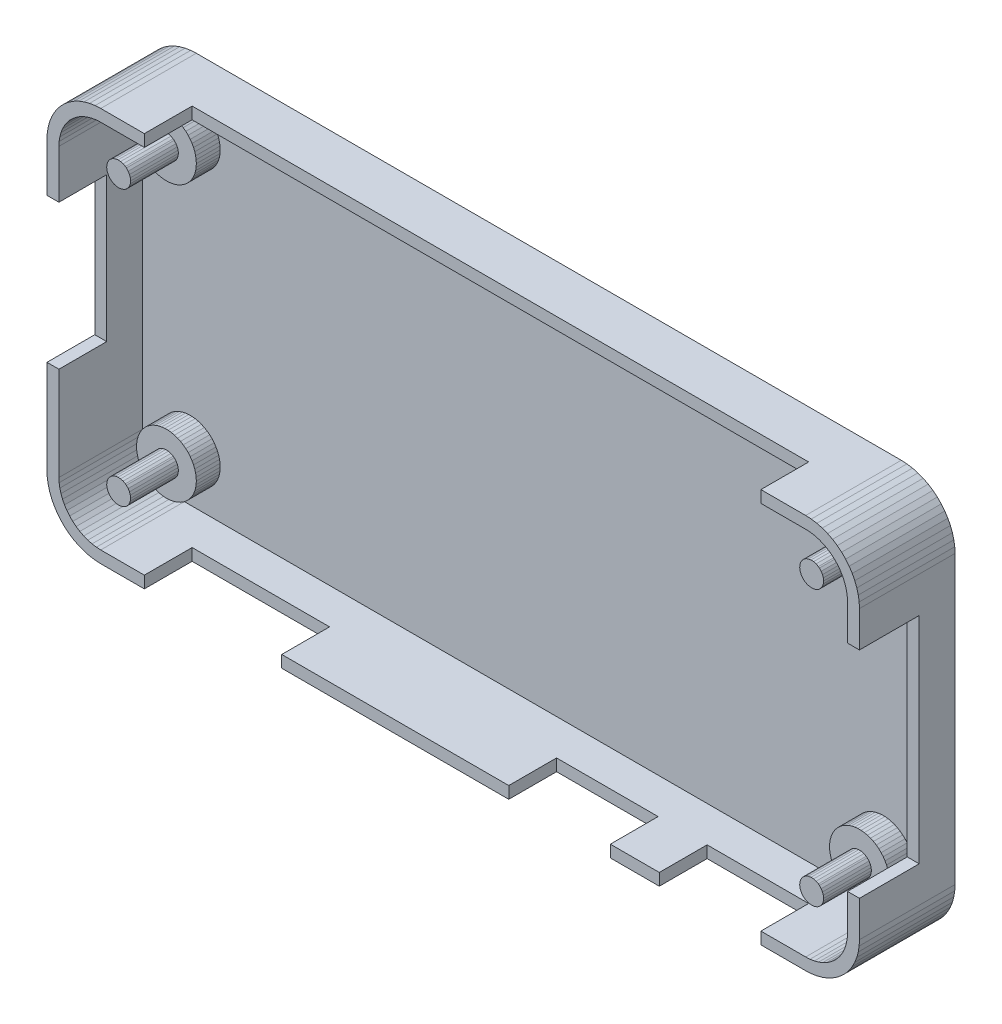
SolidWorks part; units mm, degrees
ref_plane "Front Plane" through (0, 0, 0) normal (0, 0, 1) x (1, 0, 0)
ref_plane "Top Plane" through (0, 0, 0) normal (0, 1, 0) x (1, 0, 0)
ref_plane "Right Plane" through (0, 0, 0) normal (1, 0, 0) x (0, 0, -1)
ref_plane "Plane1" through (0, 0, 0) normal (0, 0, -1) x (-1, 0, 0)
sketch "Sketch1" plane through (0, 0, 0) normal (0, 0, -1) x (-1, 0, 0)
  line L0 (29.5, 16.5) -> (-29.5, 16.5)
  line L1 (-29.5, 16.5) -> (-29.9704, 16.4753)
  line L2 (-29.9704, 16.4753) -> (-30.4356, 16.4017)
  line L3 (-30.4356, 16.4017) -> (-30.8906, 16.2798)
  line L4 (-30.8906, 16.2798) -> (-31.3303, 16.111)
  line L5 (-31.3303, 16.111) -> (-31.75, 15.8971)
  line L6 (-31.75, 15.8971) -> (-32.145, 15.6406)
  line L7 (-32.145, 15.6406) -> (-32.5111, 15.3442)
  line L8 (-32.5111, 15.3442) -> (-32.8442, 15.0111)
  line L9 (-32.8442, 15.0111) -> (-33.1406, 14.645)
  line L10 (-33.1406, 14.645) -> (-33.3971, 14.25)
  line L11 (-33.3971, 14.25) -> (-33.611, 13.8303)
  line L12 (-33.611, 13.8303) -> (-33.7798, 13.3906)
  line L13 (-33.7798, 13.3906) -> (-33.9017, 12.9356)
  line L14 (-33.9017, 12.9356) -> (-33.9753, 12.4704)
  line L15 (-33.9753, 12.4704) -> (-34, 12)
  line L16 (-34, 12) -> (-34, -12)
  line L17 (-34, -12) -> (-33.9753, -12.4704)
  line L18 (-33.9753, -12.4704) -> (-33.9017, -12.9356)
  line L19 (-33.9017, -12.9356) -> (-33.7798, -13.3906)
  line L20 (-33.7798, -13.3906) -> (-33.611, -13.8303)
  line L21 (-33.611, -13.8303) -> (-33.3971, -14.25)
  line L22 (-33.3971, -14.25) -> (-33.1406, -14.645)
  line L23 (-33.1406, -14.645) -> (-32.8442, -15.0111)
  line L24 (-32.8442, -15.0111) -> (-32.5111, -15.3442)
  line L25 (-32.5111, -15.3442) -> (-32.145, -15.6406)
  line L26 (-32.145, -15.6406) -> (-31.75, -15.8971)
  line L27 (-31.75, -15.8971) -> (-31.3303, -16.111)
  line L28 (-31.3303, -16.111) -> (-30.8906, -16.2798)
  line L29 (-30.8906, -16.2798) -> (-30.4356, -16.4017)
  line L30 (-30.4356, -16.4017) -> (-29.9704, -16.4753)
  line L31 (-29.9704, -16.4753) -> (-29.5, -16.5)
  line L32 (-29.5, -16.5) -> (29.5, -16.5)
  line L33 (29.5, -16.5) -> (29.9704, -16.4753)
  line L34 (29.9704, -16.4753) -> (30.4356, -16.4017)
  line L35 (30.4356, -16.4017) -> (30.8906, -16.2798)
  line L36 (30.8906, -16.2798) -> (31.3303, -16.111)
  line L37 (31.3303, -16.111) -> (31.75, -15.8971)
  line L38 (31.75, -15.8971) -> (32.145, -15.6406)
  line L39 (32.145, -15.6406) -> (32.5111, -15.3442)
  line L40 (32.5111, -15.3442) -> (32.8442, -15.0111)
  line L41 (32.8442, -15.0111) -> (33.1406, -14.645)
  line L42 (33.1406, -14.645) -> (33.3971, -14.25)
  line L43 (33.3971, -14.25) -> (33.611, -13.8303)
  line L44 (33.611, -13.8303) -> (33.7798, -13.3906)
  line L45 (33.7798, -13.3906) -> (33.9017, -12.9356)
  line L46 (33.9017, -12.9356) -> (33.9753, -12.4704)
  line L47 (33.9753, -12.4704) -> (34, -12)
  line L48 (34, -12) -> (34, 12)
  line L49 (34, 12) -> (33.9753, 12.4704)
  line L50 (33.9753, 12.4704) -> (33.9017, 12.9356)
  line L51 (33.9017, 12.9356) -> (33.7798, 13.3906)
  line L52 (33.7798, 13.3906) -> (33.611, 13.8303)
  line L53 (33.611, 13.8303) -> (33.3971, 14.25)
  line L54 (33.3971, 14.25) -> (33.1406, 14.645)
  line L55 (33.1406, 14.645) -> (32.8442, 15.0111)
  line L56 (32.8442, 15.0111) -> (32.5111, 15.3442)
  line L57 (32.5111, 15.3442) -> (32.145, 15.6406)
  line L58 (32.145, 15.6406) -> (31.75, 15.8971)
  line L59 (31.75, 15.8971) -> (31.3303, 16.111)
  line L60 (31.3303, 16.111) -> (30.8906, 16.2798)
  line L61 (30.8906, 16.2798) -> (30.4356, 16.4017)
  line L62 (30.4356, 16.4017) -> (29.9704, 16.4753)
  line L63 (29.9704, 16.4753) -> (29.5, 16.5)
extrude "Boss-Extrude1" add sketch "Sketch1" against normal blind 8
sketch "Sketch2" plane through (0, 0, 8) normal (0, 0, 1) x (1, 0, 0)
  line L0 (-30.5816, -15.3287) -> (-30.2277, -15.4235)
  line L1 (-30.2277, -15.4235) -> (-29.8658, -15.4808)
  line L2 (-29.8658, -15.4808) -> (-29.5, -15.5)
  line L3 (-29.5, -15.5) -> (29.5, -15.5)
  line L4 (29.5, -15.5) -> (29.8658, -15.4808)
  line L5 (29.8658, -15.4808) -> (30.2277, -15.4235)
  line L6 (30.2277, -15.4235) -> (30.5816, -15.3287)
  line L7 (30.5816, -15.3287) -> (30.9236, -15.1974)
  line L8 (30.9236, -15.1974) -> (31.25, -15.0311)
  line L9 (31.25, -15.0311) -> (31.5572, -14.8316)
  line L10 (31.5572, -14.8316) -> (31.842, -14.601)
  line L11 (31.842, -14.601) -> (32.101, -14.342)
  line L12 (32.101, -14.342) -> (32.3316, -14.0572)
  line L13 (32.3316, -14.0572) -> (32.5311, -13.75)
  line L14 (32.5311, -13.75) -> (32.6974, -13.4236)
  line L15 (32.6974, -13.4236) -> (32.8287, -13.0816)
  line L16 (32.8287, -13.0816) -> (32.9235, -12.7277)
  line L17 (32.9235, -12.7277) -> (32.9808, -12.3658)
  line L18 (32.9808, -12.3658) -> (33, -12)
  line L19 (33, -12) -> (33, 12)
  line L20 (33, 12) -> (32.9808, 12.3658)
  line L21 (32.9808, 12.3658) -> (32.9235, 12.7277)
  line L22 (32.9235, 12.7277) -> (32.8287, 13.0816)
  line L23 (32.8287, 13.0816) -> (32.6974, 13.4236)
  line L24 (32.6974, 13.4236) -> (32.5311, 13.75)
  line L25 (32.5311, 13.75) -> (32.3316, 14.0572)
  line L26 (32.3316, 14.0572) -> (32.101, 14.342)
  line L27 (32.101, 14.342) -> (31.842, 14.601)
  line L28 (31.842, 14.601) -> (31.5572, 14.8316)
  line L29 (31.5572, 14.8316) -> (31.25, 15.0311)
  line L30 (31.25, 15.0311) -> (30.9236, 15.1974)
  line L31 (30.9236, 15.1974) -> (30.5816, 15.3287)
  line L32 (30.5816, 15.3287) -> (30.2277, 15.4235)
  line L33 (30.2277, 15.4235) -> (29.8658, 15.4808)
  line L34 (29.8658, 15.4808) -> (29.5, 15.5)
  line L35 (29.5, 15.5) -> (-29.5, 15.5)
  line L36 (-29.5, 15.5) -> (-29.8658, 15.4808)
  line L37 (-29.8658, 15.4808) -> (-30.2277, 15.4235)
  line L38 (-30.2277, 15.4235) -> (-30.5816, 15.3287)
  line L39 (-30.5816, 15.3287) -> (-30.9236, 15.1974)
  line L40 (-30.9236, 15.1974) -> (-31.25, 15.0311)
  line L41 (-31.25, 15.0311) -> (-31.5572, 14.8316)
  line L42 (-31.5572, 14.8316) -> (-31.842, 14.601)
  line L43 (-31.842, 14.601) -> (-32.101, 14.342)
  line L44 (-32.101, 14.342) -> (-32.3316, 14.0572)
  line L45 (-32.3316, 14.0572) -> (-32.5311, 13.75)
  line L46 (-32.5311, 13.75) -> (-32.6974, 13.4236)
  line L47 (-32.6974, 13.4236) -> (-32.8287, 13.0816)
  line L48 (-32.8287, 13.0816) -> (-32.9235, 12.7277)
  line L49 (-32.9235, 12.7277) -> (-32.9808, 12.3658)
  line L50 (-32.9808, 12.3658) -> (-33, 12)
  line L51 (-33, 12) -> (-33, -12)
  line L52 (-33, -12) -> (-32.9808, -12.3658)
  line L53 (-32.9808, -12.3658) -> (-32.9235, -12.7277)
  line L54 (-32.9235, -12.7277) -> (-32.8287, -13.0816)
  line L55 (-32.8287, -13.0816) -> (-32.6974, -13.4236)
  line L56 (-32.6974, -13.4236) -> (-32.5311, -13.75)
  line L57 (-32.5311, -13.75) -> (-32.3316, -14.0572)
  line L58 (-32.3316, -14.0572) -> (-32.101, -14.342)
  line L59 (-32.101, -14.342) -> (-31.842, -14.601)
  line L60 (-31.842, -14.601) -> (-31.5572, -14.8316)
  line L61 (-31.5572, -14.8316) -> (-31.25, -15.0311)
  line L62 (-31.25, -15.0311) -> (-30.9236, -15.1974)
  line L63 (-30.9236, -15.1974) -> (-30.5816, -15.3287)
extrude "Cut-Extrude1" cut sketch "Sketch2" against normal blind 7
sketch "Sketch3" plane through (0, -16.5, 0) normal (0, -1, 0) x (1, 0, 0)
  line L0 (-14.35, 8) -> (-25.85, 8)
  line L1 (-25.85, 8) -> (-25.85, 4)
  line L2 (-25.85, 4) -> (-14.35, 4)
  line L3 (-14.35, 4) -> (-14.35, 8)
extrude "Cut-Extrude2" cut sketch "Sketch3" against normal up to next
sketch "Sketch4" plane through (0, -16.5, 0) normal (0, -1, 0) x (1, 0, 0)
  line L0 (13.15, 8) -> (4.65, 8)
  line L1 (4.65, 8) -> (4.65, 4)
  line L2 (4.65, 4) -> (13.15, 4)
  line L3 (13.15, 4) -> (13.15, 8)
extrude "Cut-Extrude3" cut sketch "Sketch4" against normal up to next
sketch "Sketch5" plane through (0, -16.5, 0) normal (0, -1, 0) x (1, 0, 0)
  line L0 (25.75, 8) -> (17.25, 8)
  line L1 (17.25, 8) -> (17.25, 4)
  line L2 (17.25, 4) -> (25.75, 4)
  line L3 (25.75, 4) -> (25.75, 8)
extrude "Cut-Extrude4" cut sketch "Sketch5" against normal up to next
sketch "Sketch6" plane through (-34, 0, 0) normal (-1, 0, 0) x (0, 0, 1)
  line L0 (8, -4.15) -> (8, 7.95)
  line L1 (8, 7.95) -> (4, 7.95)
  line L2 (4, 7.95) -> (4, -4.15)
  line L3 (4, -4.15) -> (8, -4.15)
extrude "Cut-Extrude5" cut sketch "Sketch6" against normal up to next
sketch "Sketch7" plane through (34, 0, 0) normal (1, 0, 0) x (0, 0, -1)
  line L0 (-8, 9) -> (-8, -9)
  line L1 (-8, -9) -> (-3, -9)
  line L2 (-3, -9) -> (-3, 9)
  line L3 (-3, 9) -> (-8, 9)
extrude "Cut-Extrude6" cut sketch "Sketch7" against normal up to next
sketch "Sketch8" plane through (0, 0, 1) normal (0, 0, 1) x (1, 0, 0)
  line L0 (-29.4045, -9.0329) -> (-29.1353, -9.0037)
  line L1 (-29.1353, -9.0037) -> (-28.8647, -9.0037)
  line L2 (-28.8647, -9.0037) -> (-28.5955, -9.0329)
  line L3 (-28.5955, -9.0329) -> (-28.3312, -9.0911)
  line L4 (-28.3312, -9.0911) -> (-28.0747, -9.1776)
  line L5 (-28.0747, -9.1776) -> (-27.829, -9.2912)
  line L6 (-27.829, -9.2912) -> (-27.597, -9.4308)
  line L7 (-27.597, -9.4308) -> (-27.3815, -9.5946)
  line L8 (-27.3815, -9.5946) -> (-27.185, -9.7808)
  line L9 (-27.185, -9.7808) -> (-27.0098, -9.9871)
  line L10 (-27.0098, -9.9871) -> (-26.8579, -10.2111)
  line L11 (-26.8579, -10.2111) -> (-26.7311, -10.4503)
  line L12 (-26.7311, -10.4503) -> (-26.6309, -10.7017)
  line L13 (-26.6309, -10.7017) -> (-26.5584, -10.9626)
  line L14 (-26.5584, -10.9626) -> (-26.5147, -11.2297)
  line L15 (-26.5147, -11.2297) -> (-26.5, -11.5)
  line L16 (-26.5, -11.5) -> (-26.5147, -11.7703)
  line L17 (-26.5147, -11.7703) -> (-26.5584, -12.0374)
  line L18 (-26.5584, -12.0374) -> (-26.6309, -12.2983)
  line L19 (-26.6309, -12.2983) -> (-26.7311, -12.5497)
  line L20 (-26.7311, -12.5497) -> (-26.8579, -12.7889)
  line L21 (-26.8579, -12.7889) -> (-27.0098, -13.0129)
  line L22 (-27.0098, -13.0129) -> (-27.185, -13.2192)
  line L23 (-27.185, -13.2192) -> (-27.3815, -13.4054)
  line L24 (-27.3815, -13.4054) -> (-27.597, -13.5692)
  line L25 (-27.597, -13.5692) -> (-27.829, -13.7088)
  line L26 (-27.829, -13.7088) -> (-28.0747, -13.8224)
  line L27 (-28.0747, -13.8224) -> (-28.3312, -13.9089)
  line L28 (-28.3312, -13.9089) -> (-28.5955, -13.9671)
  line L29 (-28.5955, -13.9671) -> (-28.8647, -13.9963)
  line L30 (-28.8647, -13.9963) -> (-29.1353, -13.9963)
  line L31 (-29.1353, -13.9963) -> (-29.4045, -13.9671)
  line L32 (-29.4045, -13.9671) -> (-29.6688, -13.9089)
  line L33 (-29.6688, -13.9089) -> (-29.9253, -13.8224)
  line L34 (-29.9253, -13.8224) -> (-30.171, -13.7088)
  line L35 (-30.171, -13.7088) -> (-30.403, -13.5692)
  line L36 (-30.403, -13.5692) -> (-30.6185, -13.4054)
  line L37 (-30.6185, -13.4054) -> (-30.815, -13.2192)
  line L38 (-30.815, -13.2192) -> (-30.9902, -13.0129)
  line L39 (-30.9902, -13.0129) -> (-31.1421, -12.7889)
  line L40 (-31.1421, -12.7889) -> (-31.2689, -12.5497)
  line L41 (-31.2689, -12.5497) -> (-31.3691, -12.2983)
  line L42 (-31.3691, -12.2983) -> (-31.4416, -12.0374)
  line L43 (-31.4416, -12.0374) -> (-31.4853, -11.7703)
  line L44 (-31.4853, -11.7703) -> (-31.5, -11.5)
  line L45 (-31.5, -11.5) -> (-31.4853, -11.2297)
  line L46 (-31.4853, -11.2297) -> (-31.4416, -10.9626)
  line L47 (-31.4416, -10.9626) -> (-31.3691, -10.7017)
  line L48 (-31.3691, -10.7017) -> (-31.2689, -10.4503)
  line L49 (-31.2689, -10.4503) -> (-31.1421, -10.2111)
  line L50 (-31.1421, -10.2111) -> (-30.9902, -9.9871)
  line L51 (-30.9902, -9.9871) -> (-30.815, -9.7808)
  line L52 (-30.815, -9.7808) -> (-30.6185, -9.5946)
  line L53 (-30.6185, -9.5946) -> (-30.403, -9.4308)
  line L54 (-30.403, -9.4308) -> (-30.171, -9.2912)
  line L55 (-30.171, -9.2912) -> (-29.9253, -9.1776)
  line L56 (-29.9253, -9.1776) -> (-29.6688, -9.0911)
  line L57 (-29.6688, -9.0911) -> (-29.4045, -9.0329)
extrude "Boss-Extrude2" add sketch "Sketch8" along normal blind 2
sketch "Sketch9" plane through (0, 0, 3) normal (0, 0, 1) x (1, 0, 0)
  line L0 (-29.9076, -11.0801) -> (-29.7961, -10.8948)
  line L1 (-29.7961, -10.8948) -> (-29.6474, -10.7378)
  line L2 (-29.6474, -10.7378) -> (-29.4684, -10.6165)
  line L3 (-29.4684, -10.6165) -> (-29.2675, -10.5364)
  line L4 (-29.2675, -10.5364) -> (-29.0541, -10.5015)
  line L5 (-29.0541, -10.5015) -> (-28.8382, -10.5132)
  line L6 (-28.8382, -10.5132) -> (-28.6299, -10.571)
  line L7 (-28.6299, -10.571) -> (-28.3903, -10.698)
  line L8 (-28.3903, -10.698) -> (-28.2039, -10.8948)
  line L9 (-28.2039, -10.8948) -> (-28.0924, -11.0801)
  line L10 (-28.0924, -11.0801) -> (-28.0234, -11.285)
  line L11 (-28.0234, -11.285) -> (-28, -11.5)
  line L12 (-28, -11.5) -> (-28.0234, -11.715)
  line L13 (-28.0234, -11.715) -> (-28.0924, -11.9199)
  line L14 (-28.0924, -11.9199) -> (-28.2039, -12.1052)
  line L15 (-28.2039, -12.1052) -> (-28.3526, -12.2622)
  line L16 (-28.3526, -12.2622) -> (-28.4388, -12.3277)
  line L17 (-28.4388, -12.3277) -> (-28.5316, -12.3835)
  line L18 (-28.5316, -12.3835) -> (-28.7325, -12.4635)
  line L19 (-28.7325, -12.4635) -> (-28.9459, -12.4985)
  line L20 (-28.9459, -12.4985) -> (-29.1618, -12.4868)
  line L21 (-29.1618, -12.4868) -> (-29.3701, -12.429)
  line L22 (-29.3701, -12.429) -> (-29.5612, -12.3277)
  line L23 (-29.5612, -12.3277) -> (-29.726, -12.1877)
  line L24 (-29.726, -12.1877) -> (-29.8569, -12.0156)
  line L25 (-29.8569, -12.0156) -> (-29.9477, -11.8193)
  line L26 (-29.9477, -11.8193) -> (-30.0059, -11.5545)
  line L27 (-30.0059, -11.5545) -> (-29.9766, -11.285)
  line L28 (-29.9766, -11.285) -> (-29.9076, -11.0801)
extrude "Boss-Extrude3" add sketch "Sketch9" along normal blind 4
sketch "Sketch10" plane through (0, 0, 1) normal (0, 0, 1) x (1, 0, 0)
  line L0 (-26.7311, 10.4503) -> (-26.8579, 10.2111)
  line L1 (-26.8579, 10.2111) -> (-27.0098, 9.9871)
  line L2 (-27.0098, 9.9871) -> (-27.185, 9.7808)
  line L3 (-27.185, 9.7808) -> (-27.3815, 9.5946)
  line L4 (-27.3815, 9.5946) -> (-27.597, 9.4308)
  line L5 (-27.597, 9.4308) -> (-27.829, 9.2912)
  line L6 (-27.829, 9.2912) -> (-28.0747, 9.1776)
  line L7 (-28.0747, 9.1776) -> (-28.3312, 9.0911)
  line L8 (-28.3312, 9.0911) -> (-28.5955, 9.0329)
  line L9 (-28.5955, 9.0329) -> (-28.8647, 9.0037)
  line L10 (-28.8647, 9.0037) -> (-29.1353, 9.0037)
  line L11 (-29.1353, 9.0037) -> (-29.4045, 9.0329)
  line L12 (-29.4045, 9.0329) -> (-29.6688, 9.0911)
  line L13 (-29.6688, 9.0911) -> (-29.9253, 9.1776)
  line L14 (-29.9253, 9.1776) -> (-30.171, 9.2912)
  line L15 (-30.171, 9.2912) -> (-30.403, 9.4308)
  line L16 (-30.403, 9.4308) -> (-30.6185, 9.5946)
  line L17 (-30.6185, 9.5946) -> (-30.815, 9.7808)
  line L18 (-30.815, 9.7808) -> (-30.9902, 9.9871)
  line L19 (-30.9902, 9.9871) -> (-31.1421, 10.2111)
  line L20 (-31.1421, 10.2111) -> (-31.2689, 10.4503)
  line L21 (-31.2689, 10.4503) -> (-31.3691, 10.7017)
  line L22 (-31.3691, 10.7017) -> (-31.4416, 10.9626)
  line L23 (-31.4416, 10.9626) -> (-31.4853, 11.2297)
  line L24 (-31.4853, 11.2297) -> (-31.5, 11.5)
  line L25 (-31.5, 11.5) -> (-31.4853, 11.7703)
  line L26 (-31.4853, 11.7703) -> (-31.4416, 12.0374)
  line L27 (-31.4416, 12.0374) -> (-31.3691, 12.2983)
  line L28 (-31.3691, 12.2983) -> (-31.2689, 12.5497)
  line L29 (-31.2689, 12.5497) -> (-31.1421, 12.7889)
  line L30 (-31.1421, 12.7889) -> (-30.9902, 13.0129)
  line L31 (-30.9902, 13.0129) -> (-30.815, 13.2192)
  line L32 (-30.815, 13.2192) -> (-30.6185, 13.4054)
  line L33 (-30.6185, 13.4054) -> (-30.403, 13.5692)
  line L34 (-30.403, 13.5692) -> (-30.171, 13.7088)
  line L35 (-30.171, 13.7088) -> (-29.9253, 13.8224)
  line L36 (-29.9253, 13.8224) -> (-29.6688, 13.9089)
  line L37 (-29.6688, 13.9089) -> (-29.4045, 13.9671)
  line L38 (-29.4045, 13.9671) -> (-29.1353, 13.9963)
  line L39 (-29.1353, 13.9963) -> (-28.8647, 13.9963)
  line L40 (-28.8647, 13.9963) -> (-28.5955, 13.9671)
  line L41 (-28.5955, 13.9671) -> (-28.3312, 13.9089)
  line L42 (-28.3312, 13.9089) -> (-28.0747, 13.8224)
  line L43 (-28.0747, 13.8224) -> (-27.829, 13.7088)
  line L44 (-27.829, 13.7088) -> (-27.597, 13.5692)
  line L45 (-27.597, 13.5692) -> (-27.3815, 13.4054)
  line L46 (-27.3815, 13.4054) -> (-27.185, 13.2192)
  line L47 (-27.185, 13.2192) -> (-27.0098, 13.0129)
  line L48 (-27.0098, 13.0129) -> (-26.8579, 12.7889)
  line L49 (-26.8579, 12.7889) -> (-26.7311, 12.5497)
  line L50 (-26.7311, 12.5497) -> (-26.6309, 12.2983)
  line L51 (-26.6309, 12.2983) -> (-26.5584, 12.0374)
  line L52 (-26.5584, 12.0374) -> (-26.5147, 11.7703)
  line L53 (-26.5147, 11.7703) -> (-26.5, 11.5)
  line L54 (-26.5, 11.5) -> (-26.5147, 11.2297)
  line L55 (-26.5147, 11.2297) -> (-26.5584, 10.9626)
  line L56 (-26.5584, 10.9626) -> (-26.6309, 10.7017)
  line L57 (-26.6309, 10.7017) -> (-26.7311, 10.4503)
extrude "Boss-Extrude4" add sketch "Sketch10" along normal blind 2
sketch "Sketch11" plane through (0, 0, 3) normal (0, 0, 1) x (1, 0, 0)
  line L0 (-29.9076, 11.9199) -> (-29.7961, 12.1052)
  line L1 (-29.7961, 12.1052) -> (-29.6474, 12.2622)
  line L2 (-29.6474, 12.2622) -> (-29.4684, 12.3835)
  line L3 (-29.4684, 12.3835) -> (-29.2675, 12.4635)
  line L4 (-29.2675, 12.4635) -> (-29.0541, 12.4985)
  line L5 (-29.0541, 12.4985) -> (-28.8382, 12.4868)
  line L6 (-28.8382, 12.4868) -> (-28.6299, 12.429)
  line L7 (-28.6299, 12.429) -> (-28.3903, 12.302)
  line L8 (-28.3903, 12.302) -> (-28.2039, 12.1052)
  line L9 (-28.2039, 12.1052) -> (-28.0924, 11.9199)
  line L10 (-28.0924, 11.9199) -> (-28.0234, 11.715)
  line L11 (-28.0234, 11.715) -> (-28, 11.5)
  line L12 (-28, 11.5) -> (-28.0234, 11.285)
  line L13 (-28.0234, 11.285) -> (-28.0924, 11.0801)
  line L14 (-28.0924, 11.0801) -> (-28.2039, 10.8948)
  line L15 (-28.2039, 10.8948) -> (-28.3526, 10.7378)
  line L16 (-28.3526, 10.7378) -> (-28.4388, 10.6723)
  line L17 (-28.4388, 10.6723) -> (-28.5316, 10.6165)
  line L18 (-28.5316, 10.6165) -> (-28.7325, 10.5364)
  line L19 (-28.7325, 10.5364) -> (-28.9459, 10.5015)
  line L20 (-28.9459, 10.5015) -> (-29.1618, 10.5132)
  line L21 (-29.1618, 10.5132) -> (-29.3701, 10.571)
  line L22 (-29.3701, 10.571) -> (-29.5612, 10.6723)
  line L23 (-29.5612, 10.6723) -> (-29.726, 10.8123)
  line L24 (-29.726, 10.8123) -> (-29.8569, 10.9844)
  line L25 (-29.8569, 10.9844) -> (-29.9477, 11.1807)
  line L26 (-29.9477, 11.1807) -> (-30.0059, 11.4455)
  line L27 (-30.0059, 11.4455) -> (-29.9766, 11.715)
  line L28 (-29.9766, 11.715) -> (-29.9076, 11.9199)
extrude "Boss-Extrude5" add sketch "Sketch11" along normal blind 4
sketch "Sketch12" plane through (0, 0, 1) normal (0, 0, 1) x (1, 0, 0)
  line L0 (30.815, -9.7808) -> (30.9902, -9.9871)
  line L1 (30.9902, -9.9871) -> (31.1421, -10.2111)
  line L2 (31.1421, -10.2111) -> (31.2689, -10.4503)
  line L3 (31.2689, -10.4503) -> (31.3691, -10.7017)
  line L4 (31.3691, -10.7017) -> (31.4416, -10.9626)
  line L5 (31.4416, -10.9626) -> (31.4853, -11.2297)
  line L6 (31.4853, -11.2297) -> (31.5, -11.5)
  line L7 (31.5, -11.5) -> (31.4853, -11.7703)
  line L8 (31.4853, -11.7703) -> (31.4416, -12.0374)
  line L9 (31.4416, -12.0374) -> (31.3691, -12.2983)
  line L10 (31.3691, -12.2983) -> (31.2689, -12.5497)
  line L11 (31.2689, -12.5497) -> (31.1421, -12.7889)
  line L12 (31.1421, -12.7889) -> (30.9902, -13.0129)
  line L13 (30.9902, -13.0129) -> (30.815, -13.2192)
  line L14 (30.815, -13.2192) -> (30.6185, -13.4054)
  line L15 (30.6185, -13.4054) -> (30.403, -13.5692)
  line L16 (30.403, -13.5692) -> (30.171, -13.7088)
  line L17 (30.171, -13.7088) -> (29.9253, -13.8224)
  line L18 (29.9253, -13.8224) -> (29.6688, -13.9089)
  line L19 (29.6688, -13.9089) -> (29.4045, -13.9671)
  line L20 (29.4045, -13.9671) -> (29.1353, -13.9963)
  line L21 (29.1353, -13.9963) -> (28.8647, -13.9963)
  line L22 (28.8647, -13.9963) -> (28.5955, -13.9671)
  line L23 (28.5955, -13.9671) -> (28.3312, -13.9089)
  line L24 (28.3312, -13.9089) -> (28.0747, -13.8224)
  line L25 (28.0747, -13.8224) -> (27.829, -13.7088)
  line L26 (27.829, -13.7088) -> (27.597, -13.5692)
  line L27 (27.597, -13.5692) -> (27.3815, -13.4054)
  line L28 (27.3815, -13.4054) -> (27.185, -13.2192)
  line L29 (27.185, -13.2192) -> (27.0098, -13.0129)
  line L30 (27.0098, -13.0129) -> (26.8579, -12.7889)
  line L31 (26.8579, -12.7889) -> (26.7311, -12.5497)
  line L32 (26.7311, -12.5497) -> (26.6309, -12.2983)
  line L33 (26.6309, -12.2983) -> (26.5584, -12.0374)
  line L34 (26.5584, -12.0374) -> (26.5147, -11.7703)
  line L35 (26.5147, -11.7703) -> (26.5, -11.5)
  line L36 (26.5, -11.5) -> (26.5147, -11.2297)
  line L37 (26.5147, -11.2297) -> (26.5584, -10.9626)
  line L38 (26.5584, -10.9626) -> (26.6309, -10.7017)
  line L39 (26.6309, -10.7017) -> (26.7311, -10.4503)
  line L40 (26.7311, -10.4503) -> (26.8579, -10.2111)
  line L41 (26.8579, -10.2111) -> (27.0098, -9.9871)
  line L42 (27.0098, -9.9871) -> (27.185, -9.7808)
  line L43 (27.185, -9.7808) -> (27.3815, -9.5946)
  line L44 (27.3815, -9.5946) -> (27.597, -9.4308)
  line L45 (27.597, -9.4308) -> (27.829, -9.2912)
  line L46 (27.829, -9.2912) -> (28.0747, -9.1776)
  line L47 (28.0747, -9.1776) -> (28.3312, -9.0911)
  line L48 (28.3312, -9.0911) -> (28.5955, -9.0329)
  line L49 (28.5955, -9.0329) -> (28.8647, -9.0037)
  line L50 (28.8647, -9.0037) -> (29.1353, -9.0037)
  line L51 (29.1353, -9.0037) -> (29.4045, -9.0329)
  line L52 (29.4045, -9.0329) -> (29.6688, -9.0911)
  line L53 (29.6688, -9.0911) -> (29.9253, -9.1776)
  line L54 (29.9253, -9.1776) -> (30.171, -9.2912)
  line L55 (30.171, -9.2912) -> (30.403, -9.4308)
  line L56 (30.403, -9.4308) -> (30.6185, -9.5946)
  line L57 (30.6185, -9.5946) -> (30.815, -9.7808)
extrude "Boss-Extrude6" add sketch "Sketch12" along normal blind 2
sketch "Sketch13" plane through (0, 0, 3) normal (0, 0, 1) x (1, 0, 0)
  line L0 (28.0924, -11.0801) -> (28.2039, -10.8948)
  line L1 (28.2039, -10.8948) -> (28.3526, -10.7378)
  line L2 (28.3526, -10.7378) -> (28.5316, -10.6165)
  line L3 (28.5316, -10.6165) -> (28.7325, -10.5364)
  line L4 (28.7325, -10.5364) -> (28.9459, -10.5015)
  line L5 (28.9459, -10.5015) -> (29.1618, -10.5132)
  line L6 (29.1618, -10.5132) -> (29.3701, -10.571)
  line L7 (29.3701, -10.571) -> (29.6097, -10.698)
  line L8 (29.6097, -10.698) -> (29.7961, -10.8948)
  line L9 (29.7961, -10.8948) -> (29.9076, -11.0801)
  line L10 (29.9076, -11.0801) -> (29.9766, -11.285)
  line L11 (29.9766, -11.285) -> (30, -11.5)
  line L12 (30, -11.5) -> (29.9766, -11.715)
  line L13 (29.9766, -11.715) -> (29.9076, -11.9199)
  line L14 (29.9076, -11.9199) -> (29.7961, -12.1052)
  line L15 (29.7961, -12.1052) -> (29.6474, -12.2622)
  line L16 (29.6474, -12.2622) -> (29.5612, -12.3277)
  line L17 (29.5612, -12.3277) -> (29.4684, -12.3835)
  line L18 (29.4684, -12.3835) -> (29.2675, -12.4635)
  line L19 (29.2675, -12.4635) -> (29.0541, -12.4985)
  line L20 (29.0541, -12.4985) -> (28.8382, -12.4868)
  line L21 (28.8382, -12.4868) -> (28.6299, -12.429)
  line L22 (28.6299, -12.429) -> (28.4388, -12.3277)
  line L23 (28.4388, -12.3277) -> (28.274, -12.1877)
  line L24 (28.274, -12.1877) -> (28.1431, -12.0156)
  line L25 (28.1431, -12.0156) -> (28.0523, -11.8193)
  line L26 (28.0523, -11.8193) -> (27.9941, -11.5545)
  line L27 (27.9941, -11.5545) -> (28.0234, -11.285)
  line L28 (28.0234, -11.285) -> (28.0924, -11.0801)
extrude "Boss-Extrude7" add sketch "Sketch13" along normal blind 4
sketch "Sketch14" plane through (0, 0, 1) normal (0, 0, 1) x (1, 0, 0)
  line L0 (31.3691, 10.7017) -> (31.2689, 10.4503)
  line L1 (31.2689, 10.4503) -> (31.1421, 10.2111)
  line L2 (31.1421, 10.2111) -> (30.9902, 9.9871)
  line L3 (30.9902, 9.9871) -> (30.815, 9.7808)
  line L4 (30.815, 9.7808) -> (30.6185, 9.5946)
  line L5 (30.6185, 9.5946) -> (30.403, 9.4308)
  line L6 (30.403, 9.4308) -> (30.171, 9.2912)
  line L7 (30.171, 9.2912) -> (29.9253, 9.1776)
  line L8 (29.9253, 9.1776) -> (29.6688, 9.0911)
  line L9 (29.6688, 9.0911) -> (29.4045, 9.0329)
  line L10 (29.4045, 9.0329) -> (29.1353, 9.0037)
  line L11 (29.1353, 9.0037) -> (28.8647, 9.0037)
  line L12 (28.8647, 9.0037) -> (28.5955, 9.0329)
  line L13 (28.5955, 9.0329) -> (28.3312, 9.0911)
  line L14 (28.3312, 9.0911) -> (28.0747, 9.1776)
  line L15 (28.0747, 9.1776) -> (27.829, 9.2912)
  line L16 (27.829, 9.2912) -> (27.597, 9.4308)
  line L17 (27.597, 9.4308) -> (27.3815, 9.5946)
  line L18 (27.3815, 9.5946) -> (27.185, 9.7808)
  line L19 (27.185, 9.7808) -> (27.0098, 9.9871)
  line L20 (27.0098, 9.9871) -> (26.8579, 10.2111)
  line L21 (26.8579, 10.2111) -> (26.7311, 10.4503)
  line L22 (26.7311, 10.4503) -> (26.6309, 10.7017)
  line L23 (26.6309, 10.7017) -> (26.5584, 10.9626)
  line L24 (26.5584, 10.9626) -> (26.5147, 11.2297)
  line L25 (26.5147, 11.2297) -> (26.5, 11.5)
  line L26 (26.5, 11.5) -> (26.5147, 11.7703)
  line L27 (26.5147, 11.7703) -> (26.5584, 12.0374)
  line L28 (26.5584, 12.0374) -> (26.6309, 12.2983)
  line L29 (26.6309, 12.2983) -> (26.7311, 12.5497)
  line L30 (26.7311, 12.5497) -> (26.8579, 12.7889)
  line L31 (26.8579, 12.7889) -> (27.0098, 13.0129)
  line L32 (27.0098, 13.0129) -> (27.185, 13.2192)
  line L33 (27.185, 13.2192) -> (27.3815, 13.4054)
  line L34 (27.3815, 13.4054) -> (27.597, 13.5692)
  line L35 (27.597, 13.5692) -> (27.829, 13.7088)
  line L36 (27.829, 13.7088) -> (28.0747, 13.8224)
  line L37 (28.0747, 13.8224) -> (28.3312, 13.9089)
  line L38 (28.3312, 13.9089) -> (28.5955, 13.9671)
  line L39 (28.5955, 13.9671) -> (28.8647, 13.9963)
  line L40 (28.8647, 13.9963) -> (29.1353, 13.9963)
  line L41 (29.1353, 13.9963) -> (29.4045, 13.9671)
  line L42 (29.4045, 13.9671) -> (29.6688, 13.9089)
  line L43 (29.6688, 13.9089) -> (29.9253, 13.8224)
  line L44 (29.9253, 13.8224) -> (30.171, 13.7088)
  line L45 (30.171, 13.7088) -> (30.403, 13.5692)
  line L46 (30.403, 13.5692) -> (30.6185, 13.4054)
  line L47 (30.6185, 13.4054) -> (30.815, 13.2192)
  line L48 (30.815, 13.2192) -> (30.9902, 13.0129)
  line L49 (30.9902, 13.0129) -> (31.1421, 12.7889)
  line L50 (31.1421, 12.7889) -> (31.2689, 12.5497)
  line L51 (31.2689, 12.5497) -> (31.3691, 12.2983)
  line L52 (31.3691, 12.2983) -> (31.4416, 12.0374)
  line L53 (31.4416, 12.0374) -> (31.4853, 11.7703)
  line L54 (31.4853, 11.7703) -> (31.5, 11.5)
  line L55 (31.5, 11.5) -> (31.4853, 11.2297)
  line L56 (31.4853, 11.2297) -> (31.4416, 10.9626)
  line L57 (31.4416, 10.9626) -> (31.3691, 10.7017)
extrude "Boss-Extrude8" add sketch "Sketch14" along normal blind 2
sketch "Sketch15" plane through (0, 0, 3) normal (0, 0, 1) x (1, 0, 0)
  line L0 (28.0924, 11.9199) -> (28.2039, 12.1052)
  line L1 (28.2039, 12.1052) -> (28.3526, 12.2622)
  line L2 (28.3526, 12.2622) -> (28.5316, 12.3835)
  line L3 (28.5316, 12.3835) -> (28.7325, 12.4635)
  line L4 (28.7325, 12.4635) -> (28.9459, 12.4985)
  line L5 (28.9459, 12.4985) -> (29.1618, 12.4868)
  line L6 (29.1618, 12.4868) -> (29.3701, 12.429)
  line L7 (29.3701, 12.429) -> (29.6097, 12.302)
  line L8 (29.6097, 12.302) -> (29.7961, 12.1052)
  line L9 (29.7961, 12.1052) -> (29.9076, 11.9199)
  line L10 (29.9076, 11.9199) -> (29.9766, 11.715)
  line L11 (29.9766, 11.715) -> (30, 11.5)
  line L12 (30, 11.5) -> (29.9766, 11.285)
  line L13 (29.9766, 11.285) -> (29.9076, 11.0801)
  line L14 (29.9076, 11.0801) -> (29.7961, 10.8948)
  line L15 (29.7961, 10.8948) -> (29.6474, 10.7378)
  line L16 (29.6474, 10.7378) -> (29.5612, 10.6723)
  line L17 (29.5612, 10.6723) -> (29.4684, 10.6165)
  line L18 (29.4684, 10.6165) -> (29.2675, 10.5364)
  line L19 (29.2675, 10.5364) -> (29.0541, 10.5015)
  line L20 (29.0541, 10.5015) -> (28.8382, 10.5132)
  line L21 (28.8382, 10.5132) -> (28.6299, 10.571)
  line L22 (28.6299, 10.571) -> (28.4388, 10.6723)
  line L23 (28.4388, 10.6723) -> (28.274, 10.8123)
  line L24 (28.274, 10.8123) -> (28.1431, 10.9844)
  line L25 (28.1431, 10.9844) -> (28.0523, 11.1807)
  line L26 (28.0523, 11.1807) -> (27.9941, 11.4455)
  line L27 (27.9941, 11.4455) -> (28.0234, 11.715)
  line L28 (28.0234, 11.715) -> (28.0924, 11.9199)
extrude "Boss-Extrude9" add sketch "Sketch15" along normal blind 4
chamfer "Chamfer1" distance 0.0549 angle 9.31 2 edges at (27.9941, 11.4455, 5) (-30.0059, 11.4455, 5) first distance on face at (28.0232, 11.3131, 5) first distance on face at (-29.9768, 11.3131, 5)
chamfer "Chamfer2" distance 0.0549 angle 9.31 2 edges at (27.9941, -11.5545, 5) (-30.0059, -11.5545, 5) first distance on face at (28.0232, -11.6869, 5) first distance on face at (-29.9768, -11.6869, 5)
chamfer "Chamfer3" distance 0.0549 angle 9.311 1 edges at (-28.3903, 12.302, 5) first distance on face at (-28.5101, 12.3655, 5)
chamfer "Chamfer4" distance 0.0549 angle 9.31 1 edges at (29.6097, 12.302, 5) first distance on face at (29.4899, 12.3655, 5)
chamfer "Chamfer5" distance 0.0549 angle 9.312 1 edges at (-28.3903, -10.698, 5) first distance on face at (-28.5101, -10.6345, 5)
chamfer "Chamfer6" distance 0.0549 angle 9.311 1 edges at (29.6097, -10.698, 5) first distance on face at (29.4899, -10.6345, 5)
sketch "Sketch16" plane through (0, 16.5, 0) normal (0, 1, 0) x (-1, 0, 0)
  line L0 (25.85, 8) -> (-25.75, 8)
  line L1 (25.85, 8) -> (25.85, 4)
  line L2 (25.85, 4) -> (-25.75, 4)
  line L3 (-25.75, 8) -> (-25.75, 4)
extrude "Cut-Extrude7" cut sketch "Sketch16" against normal blind 10
